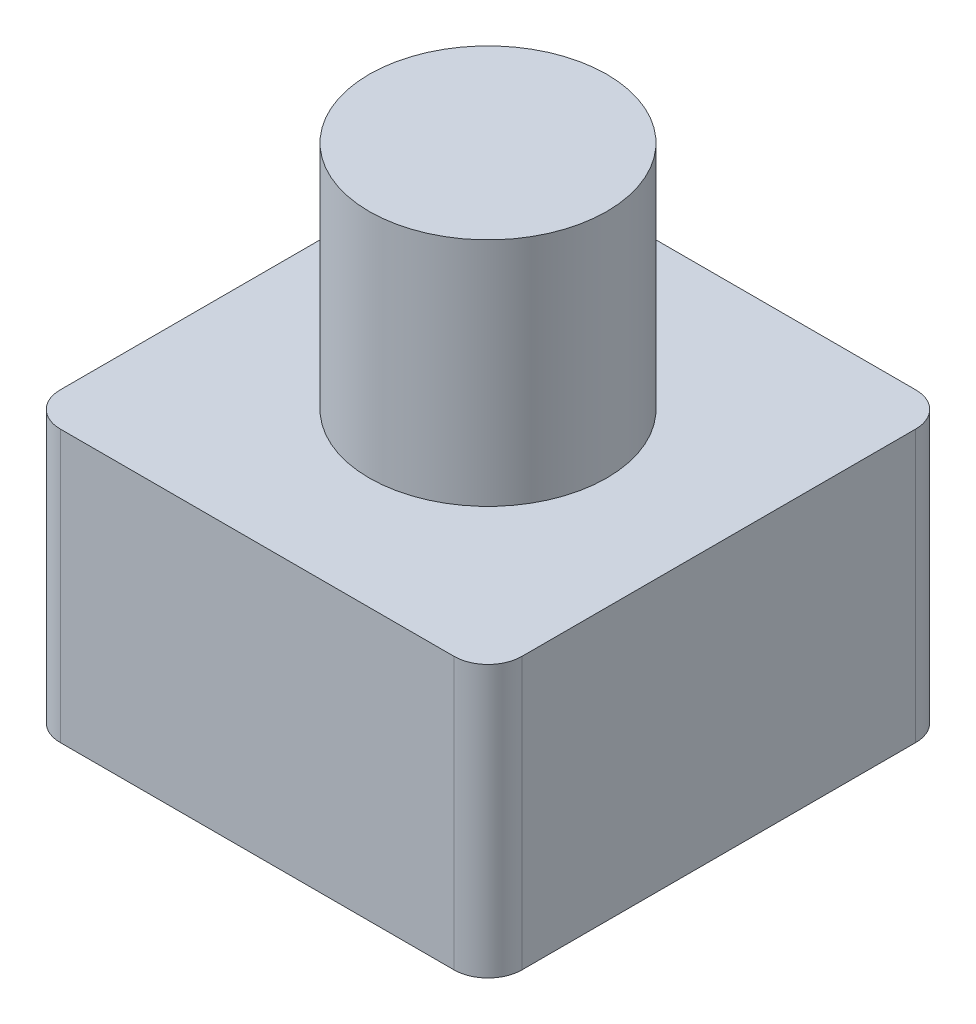
SolidWorks part; units mm, degrees
ref_plane "Front Plane" through (0, 0, 0) normal (0, 0, 1) x (1, 0, 0)
ref_plane "Top Plane" through (0, 0, 0) normal (0, 1, 0) x (1, 0, 0)
ref_plane "Right Plane" through (0, 0, 0) normal (1, 0, 0) x (0, 0, -1)
sketch "Sketch1" plane through (0, 0, 0) normal (0, 1, 0) x (1, 0, 0)
  line L1 (-29, 34) -> (29, 34)
  line L2 (-34, 29) -> (-34, -29)
  line L3 (-29, -34) -> (29, -34)
  line L4 (34, 29) -> (34, -29)
  arc A0 (29, -34) -> (34, -29) centre (29, -29) ccw
  arc A1 (-34, -29) -> (-29, -34) centre (-29, -29) ccw
  arc A2 (29, 34) -> (34, 29) centre (29, 29) cw
  arc A3 (-29, 34) -> (-34, 29) centre (-29, 29) ccw
  point P4 (-34, 0)
  point P5 (0, 34)
  point P11 (-34, -34)
  point P16 (-34, 34)
  dimension "D2" = 5
  dimension "D1" = 68
extrude "Boss-Extrude1" add sketch "Sketch1" along normal blind 40 contours L2 A1 L3 A0 L4 A2 L1 A3
sketch "Sketch2" plane through (0, 40, 0) normal (0, 1, 0) x (1, 0, 0)
  circle A0 centre (0, 0) radius 17.5
  dimension "D1" = 35
extrude "Boss-Extrude2" add sketch "Sketch2" along normal blind 34
sketch "Sketch3" plane through (0, 40, 0) normal (0, 1, 0) x (1, 0, 0)
  line L0 (-51.7219, 0) -> (58.4879, 0) construction
  line L1 (0, 43.0003) -> (0, -45.4197) construction
  circle A0 centre (-20, 20) radius 3.1675
  point P6 (-51.7219, 0)
  dimension "D1" = 20
  dimension "D3" = 6.335
  dimension "D2" = 20
